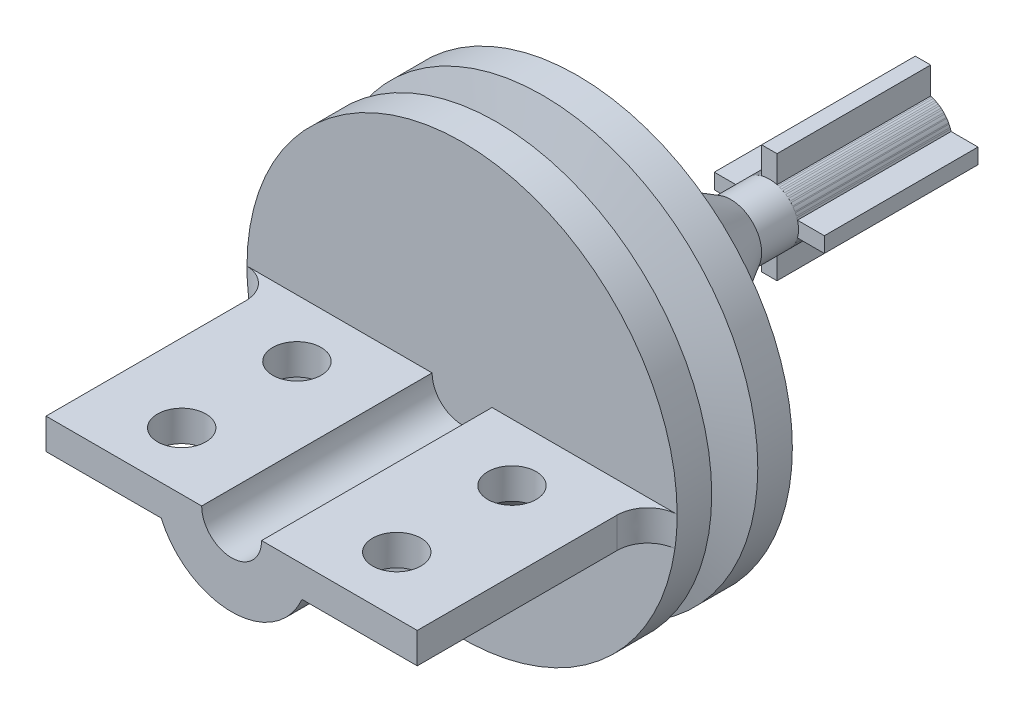
SolidWorks part; units mm, degrees
ref_plane "Front Plane" through (0, 0, 0) normal (0, 0, 1) x (1, 0, 0)
ref_plane "Top Plane" through (0, 0, 0) normal (0, 1, 0) x (1, 0, 0)
ref_plane "Right Plane" through (0, 0, 0) normal (1, 0, 0) x (0, 0, -1)
sketch "Sketch2" plane through (0, 0, 0) normal (1, 0, 0) x (0, 0, -1)
  line L0 (15, 5) -> (15, 10)
  line L1 (0, 0) -> (15, 0)
  line L2 (0, 0) -> (0, 5)
  line L3 (0, 5) -> (15, 5)
  line L4 (15, 0) -> (15, 5) construction
  line L5 (15, 0) -> (22.5, 0)
  line L6 (15, 0) -> (15, 10) construction
  line L7 (15, 10) -> (22.5, 10) construction
  line L8 (22.5, 0) -> (22.5, 10) construction
  line L9 (22.5, 0) -> (45, 0)
  line L10 (22.5, 0) -> (22.5, 1.9) construction
  line L11 (22.5, 1.9) -> (45, 1.9)
  line L12 (45, 0) -> (45, 1.9)
  line L13 (22.5, 10) -> (22.5, 1.9)
  line L14 (15, 10) -> (15, 14)
  line L15 (15, 14) -> (17.25, 14)
  line L16 (17.25, 14) -> (18.25, 10)
  line L17 (18.25, 10) -> (19.25, 10)
  line L18 (20.25, 14) -> (22.5, 14)
  line L19 (22.5, 14) -> (22.5, 10)
  line L20 (19.25, 10) -> (20.25, 14)
  line L21 (0, 0) -> (48.9459, 0) construction
  line L22 (19.25, 10) -> (19.25, 14) construction
  line L23 (19.25, 14) -> (20.25, 14) construction
  line L24 (18.25, 10) -> (18.25, 14) construction
  line L25 (18.25, 14) -> (17.25, 14) construction
  line L27 (22.5, 5) -> (32.5, 5)
  line L28 (22.5, 5) -> (22.5, 0)
  line L29 (22.5, 0) -> (32.5, 0)
  line L30 (32.5, 5) -> (32.5, 0)
  point P21 (18.75, 10)
  dimension "D1" = 5
  dimension "D2" = 1.9
  dimension "D3" = 10
  dimension "D4" = 15
  dimension "D5" = 7.5
  dimension "D6" = 1
  dimension "D7" = 4
  dimension "D8" = 1
  dimension "D9" = 22.5
  dimension "D10" = 12.5
  dimension "D11" = 5
revolve "Revolve1" add sketch "Sketch2" angle 360 about L21 region at (0, 4.7897, -13.8445) region at (0, 0.95, -38.75) region at (0, 3.45, -27.5)
sketch "Sketch3" plane through (0, 0, 0) normal (0, 0, 1) x (1, 0, 0)
  circle A0 centre (0, 0) radius 1.95
  dimension "D1" = 3.9
extrude "Cut-Extrude1" cut sketch "Sketch3" against normal blind 15
sketch "Sketch4" plane through (0, 0, -45) normal (0, 0, -1) x (-1, 0, 0)
  line L0 (0, 14) -> (0, 3.583) construction
  line L1 (-14, 0) -> (14, 0) construction
  line L2 (0, -3.583) -> (0, -14) construction
  line L3 (-0.5, -3.583) -> (0.5, -3.583)
  line L4 (-0.5, -3.583) -> (-0.5, -1.833)
  line L5 (-0.5, 3.583) -> (0.5, 3.583)
  line L6 (0.5, -3.583) -> (0.5, -1.833)
  line L7 (-0.5, 1.833) -> (-0.5, 3.583)
  line L8 (0.5, 1.833) -> (0.5, 3.583)
  line L9 (0, 3.583) -> (0, -3.583) construction
  line L10 (1.833, 0.5) -> (3.583, 0.5)
  line L11 (-3.583, -0.5) -> (-1.833, -0.5)
  line L12 (-3.583, -0.5) -> (-3.583, 0.5)
  line L13 (-3.583, 0.5) -> (-1.833, 0.5)
  line L14 (3.583, -0.5) -> (3.583, 0.5)
  line L18 (1.833, -0.5) -> (3.583, -0.5)
  circle A0 centre (0, 0) radius 14 construction
  arc A1 (-0.5, 1.833) -> (-1.833, 0.5) centre (0, 0) ccw
  circle A2 centre (0, 0) radius 1.9 construction
  arc A3 (-1.833, -0.5) -> (-0.5, -1.833) centre (0, 0) ccw
  arc A4 (0.5, -1.833) -> (1.833, -0.5) centre (0, 0) ccw
  arc A5 (1.833, 0.5) -> (0.5, 1.833) centre (0, 0) ccw
  point P7 (0, 0)
  dimension "D5" = 0.5
  dimension "D1" = 1
  dimension "D2" = 1.75
  dimension "D3" = 1.75
  dimension "D4" = 1
  dimension "D6" = 1
  dimension "D7" = 1
  dimension "D8" = 1.75
  dimension "D9" = 1.75
  dimension "D10" = 1
  dimension "D11" = 0.5
extrude "Boss-Extrude1" add sketch "Sketch4" against normal blind 10 contours L7 L5 L8 A5 L10 L14 L18 A4 L6 L3 L4 A3 L11 L12 L13 A1
sketch "Sketch5" plane through (0, 0, -15) normal (0, 0, 1) x (1, 0, 0)
  line L0 (14, 0) -> (-14, 0) construction
  line L1 (-8.794, 0) -> (9.4211, 0)
  line L2 (-8.794, 0) -> (-8.794, 7.3811)
  line L3 (-8.794, 7.3811) -> (9.4211, 7.3811)
  line L4 (9.4211, 0) -> (9.4211, 7.3811)
extrude "Cut-Extrude3" cut sketch "Sketch5" along normal blind 29
sketch "Sketch6" plane through (0, 0, -15) normal (0, 0, 1) x (1, 0, 0)
  line L0 (5, 0) -> (12.0826, 0)
  line L1 (14, 0) -> (-14, 0) construction
  line L2 (12.0826, 0) -> (12.0826, -2)
  line L3 (12.0826, -2) -> (4.5826, -2)
  line L4 (0, 8.5096) -> (0, 0) construction
  line L5 (0, 14) -> (0, 3.583) construction
  line L6 (-12.0826, -2) -> (-4.5826, -2)
  line L7 (-12.0826, 0) -> (-12.0826, -2)
  line L8 (-5, 0) -> (-12.0826, 0)
  arc A0 (-5, 0) -> (5, 0) centre (0, 0) ccw construction
  arc A1 (-5, 0) -> (5, 0) centre (0, 0) ccw construction
  arc A2 (5, 0) -> (4.5826, -2) centre (0, 0) cw
  arc A3 (-5, 0) -> (-4.5826, -2) centre (0, 0) ccw
  dimension "D1" = 2
  dimension "D2" = 7.5
extrude "Boss-Extrude2" add sketch "Sketch6" along normal up to surface (15 mm away) up to face at (0, -1.7375, 0)
sketch "Sketch7" plane through (0, 0, 0) normal (0, 1, 0) x (1, 0, 0)
  line L0 (0, 0) -> (0, 15) construction
  line L1 (-1.95, 15) -> (1.95, 15) construction
  line L4 (-12.0826, 7.5) -> (12.0826, 7.5) construction
  line L5 (-12.0826, 0) -> (-12.0826, 15) construction
  line L6 (12.0826, 0) -> (12.0826, 15) construction
  circle A2 centre (-7, 11.25) radius 1.575
  circle A3 centre (-7, 3.75) radius 1.575
  circle A4 centre (7, 3.75) radius 1.575
  circle A5 centre (7, 11.25) radius 1.575
  dimension "D2" = 7
  dimension "D1" = 3.15
  dimension "D3" = 3.75
extrude "Cut-Extrude4" cut sketch "Sketch7" against normal through all both and the other way through all
fillet "Fillet3" radius 2.5 1 edges at (5, 0, -22.5)
fillet "Fillet4" radius 2 3 edges at (-12.0826, -1, -15) (12.0826, -1, -15) (0, -5, -15)
sketch "Sketch8" plane through (0, 0, 0) normal (0, 0, 1) x (1, 0, 0)
  line L0 (0, -3.583) -> (0, -14) construction
  circle A0 centre (0, -12) radius 1
  dimension "D1" = 2
  dimension "D2" = 12
extrude "Cut-Extrude5" cut sketch "Sketch8" against normal through all both and the other way through all
chamfer "Chamfer6" distance 3 angle 60 1 edges at (5, 0, -32.5) first distance on face at (1.9, 0, -32.5)
